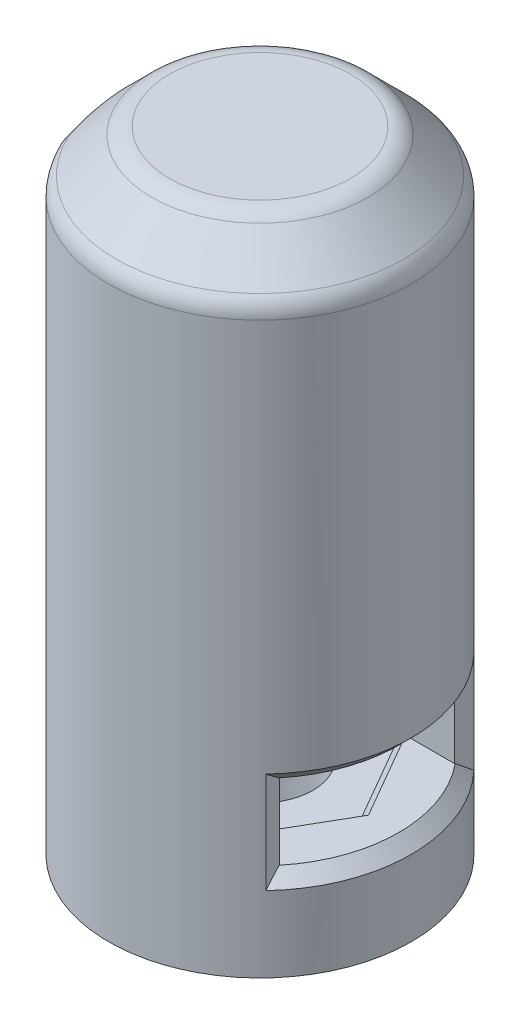
SolidWorks part; units mm, degrees
material "ABS"
ref_plane "Front Plane" through (0, 0, 0) normal (0, 0, 1) x (1, 0, 0)
ref_plane "Top Plane" through (0, 0, 0) normal (0, 1, 0) x (1, 0, 0)
ref_plane "Right Plane" through (0, 0, 0) normal (1, 0, 0) x (0, 0, -1)
sketch "Sketch1" plane through (0, 0, 0) normal (0, 1, 0) x (1, 0, 0)
  circle A0 centre (0, 0) radius 6
  dimension "D1" = 12
extrude "Base Extrude" add sketch "Sketch1" along normal mid plane 25
chamfer "Top Chemfer" distance 2 angle 45 1 edges at (0, 12.5, 6)
sketch "Sketch2" plane through (0, 0, 0) normal (1, 0, 0) x (0, 0, -1)
  line L0 (6, -12.5) -> (6, 10.5) construction
  line L1 (-6, -12.5) -> (6, -12.5)
  line L2 (-6, -12.5) -> (-6, 12.5)
  line L3 (-6, 12.5) -> (6, 12.5)
  line L4 (6, -12.5) -> (6, 12.5)
  line L5 (4, 12.5) -> (-4, 12.5) construction
extrude "Side Flatten Cut" cut sketch "Sketch2" against normal blind 25 from offset 5.5 offset against normal yes
fillet "Edges Fillet" radius 1 5 edges at (0, 12.5, 4) (6, 10.5, 0) (-5.5, -1, 2.3979) (-5.5, 10.9993, 0.0859) (-5.5, -1, -2.3979)
sketch "Sketch3" plane through (0, 0, 0) normal (0, 1, 0) x (1, 0, 0)
  line L1 (2.0063, -3.475) -> (4.0126, 0)
  line L2 (4.0126, 0) -> (2.0063, 3.475)
  line L3 (2.0063, 3.475) -> (-2.0063, 3.475)
  line L4 (-2.0063, 3.475) -> (-4.0126, 0)
  line L5 (-4.0126, 0) -> (-2.0063, -3.475)
  line L6 (-2.0063, -3.475) -> (2.0063, -3.475)
  circle A0 centre (0, 0) radius 3.475 construction
  dimension "D1" = 6.95
extrude "Nut Cut" cut sketch "Sketch3" against normal blind 3.25 from offset 6 offset against normal yes
sketch "Sketch5" plane through (0, 0, 0) normal (1, 0, 0) x (0, 0, -1)
  line L0 (0, -6) -> (-3.475, -6) construction
  line L1 (-3.475, -6) -> (3.475, -6)
  line L2 (-3.475, -6) -> (-3.475, -9)
  line L3 (-3.475, -9) -> (3.475, -9)
  line L4 (3.475, -6) -> (3.475, -9)
  point P6 (0, -6)
  dimension "D1" = 3
  dimension "D2" = 6.95
extrude "Nut Insert Cut" cut sketch "Sketch5" along normal through all
chamfer "Nut Insert Chamfer 1" distance 0.25 angle 45 2 edges at (3.0094, -9, 1.7375) (3.0094, -9, -1.7375)
chamfer "Nut Insert Chamfer 2" distance 0.5 angle 45 2 edges at (6, -9, 0) (6, -6, 0)
chamfer "Nut Insert Chamfer 3" distance 0.9 angle 45 2 edges at (4.8913, -7.5, -3.475) (4.8913, -7.5, 3.475) first distance on face at (0.3, -1.2071, 0)
sketch "Sketch6" plane through (0, -12.5, 0) normal (0, -1, 0) x (1, 0, 0)
  circle A0 centre (0, 0) radius 2.1
  dimension "D1" = 4.2
extrude "Bolt Cut" cut sketch "Sketch6" against normal blind 20
